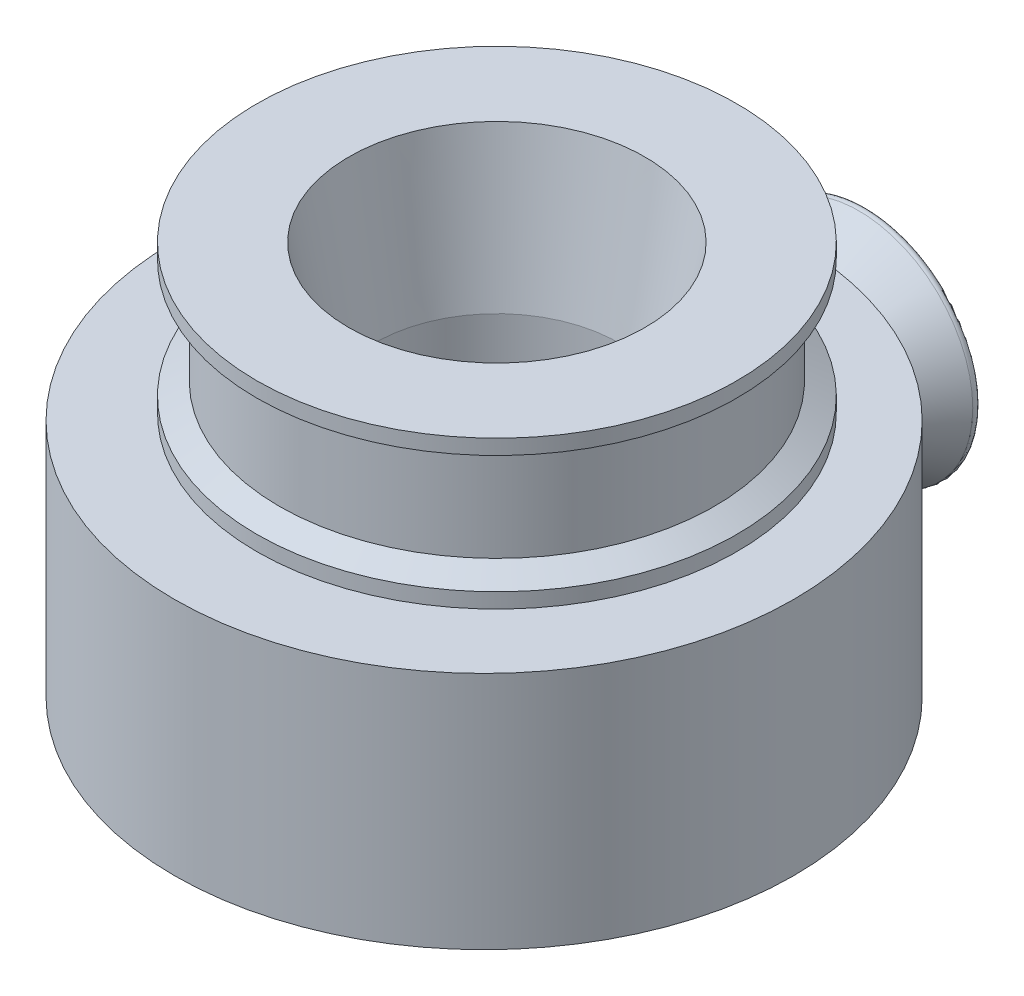
SolidWorks part; units mm, degrees
ref_plane "Front Plane" through (0, 0, 0) normal (0, 0, 1) x (1, 0, 0)
ref_plane "Top Plane" through (0, 0, 0) normal (0, 1, 0) x (1, 0, 0)
ref_plane "Right Plane" through (0, 0, 0) normal (1, 0, 0) x (0, 0, -1)
sketch "Sketch1" plane through (0, 0, 0) normal (0, 1, 0) x (1, 0, 0)
  circle A0 centre (0, 0) radius 20.65
  circle A1 centre (0, 0) radius 12.75
  dimension "D1" = 41.3
  dimension "D2" = 25.5
extrude "Boss-Extrude1" add sketch "Sketch1" along normal mid plane 15.95
sketch "Sketch2" plane through (0, 0, 0) normal (0, 1, 0) x (1, 0, 0)
  line L0 (-7.35, 25.45) -> (7.35, 25.45)
  line L1 (-4.285, 20.2005) -> (4.285, 20.2005)
  line L2 (-4.285, 20.2005) -> (-7.5966, 24.9791)
  line L3 (4.285, 20.2005) -> (7.5966, 24.9791) construction
  line L4 (0, 25.45) -> (0, 20.2005)
  line L5 (0, 0) -> (0, -7.3566) construction
  circle A0 centre (0, 0) radius 20.65 construction
  arc A1 (-7.35, 25.45) -> (-7.5966, 24.9791) centre (-7.35, 25.15) ccw
  arc A2 (7.35, 25.45) -> (7.5966, 24.9791) centre (7.35, 25.15) cw
  point P2 (0, 20.65)
  point P3 (0, 25.45)
  point P13 (7.65, 25.15)
  point P14 (-7.65, 25.15)
  dimension "D3" = 15.3
  dimension "D4" = 0.3
  dimension "D1" = 4.8
  dimension "D2" = 8.57
ref_axis "Axis1" through (0, 0, 23) along (0, 0, -1)
revolve "Revolve1" add sketch "Sketch2" angle 360 about axis through (0, 0, 23) along (0, 0, -1) region at (-3.1318, 0, -23.0808)
sketch "Sketch3" plane through (0, 0, -25.45) normal (0, 0, -1) x (-1, 0, 0)
  line L1 (0, 2.6558) -> (-2.3, 1.3279)
  line L2 (-2.3, 1.3279) -> (-2.3, -1.3279)
  line L3 (-2.3, -1.3279) -> (0, -2.6558)
  line L4 (0, -2.6558) -> (2.3, -1.3279)
  line L5 (2.3, -1.3279) -> (2.3, 1.3279)
  line L6 (2.3, 1.3279) -> (0, 2.6558)
  circle A0 centre (0, 0) radius 2.3 construction
  dimension "D1" = 4.6
extrude "Cut-Extrude1" cut sketch "Sketch3" against normal blind 4.6
sketch "Sketch4" plane through (0, 0, 0) normal (0, 1, 0) x (1, 0, 0)
  line L0 (-3.5, 12.95) -> (3.5, 12.95)
  line L1 (7.35, 25.45) -> (-7.35, 25.45) construction
  line L2 (-3.5, 12.95) -> (-4.45, 11.9482)
  line L3 (-4.45, 11.9482) -> (4.45, 11.9482)
  line L4 (4.45, 11.9482) -> (3.5, 12.95)
  line L5 (0, 12.95) -> (0, 11.9482)
  circle A0 centre (0, 0) radius 12.75 construction
  dimension "D1" = 12.5
  dimension "D2" = 8.9
  dimension "D3" = 7
revolve "Cut-Revolve2" cut sketch "Sketch4" angle 360 about axis through (0, 0, 23) along (0, 0, -1) region at (-1.997, 0, -12.4292)
sketch "Sketch5" plane through (0, 0, 0) normal (0, 1, 0) x (1, 0, 0)
  line L0 (0, -23) -> (0, 28.7) construction
  circle A0 centre (0, 0) radius 12.55
  circle A1 centre (0, 0.8509) radius 8.125
  circle A2 centre (0, 0) radius 12.75 construction
  dimension "D1" = 0.2
  dimension "D2" = 16.25
  dimension "D3" = 0.8509
extrude "Boss-Extrude2" add sketch "Sketch5" along normal up to surface and the other way up to surface separate body up to face at (0, 7.975, 20.65) other way up to face at (0, -7.975, 20.65)
sketch "Sketch9" plane through (0, 0, -25.45) normal (0, 0, -1) x (-1, 0, 0)
  circle A0 centre (0, 0) radius 3
  dimension "D1" = 6
extrude "Cut-Extrude3" cut sketch "Sketch9" against normal blind 13.97
chamfer "Chamfer1" distance 1.016 angle 45 1 edges at (-3, 0, -11.48)
mirror "Mirror2" about plane through (0, 0, 0) normal (0, 0, 1) of "Chamfer1", "Cut-Extrude3"
ref_axis "Axis2" through (0, 69.5801, -0.8509) along (0, -1, 0)
sketch "Sketch11" plane through (0, 0, 0) normal (1, 0, 0) x (0, 0, -1)
  line L0 (8.9759, 7.975) -> (10.7155, 17.841)
  line L3 (10.7155, 17.841) -> (16.8509, 17.841)
  line L4 (16.8509, 17.841) -> (16.8509, 16.841)
  line L5 (16.8509, 16.841) -> (15.3509, 16.841)
  line L6 (15.3509, 16.841) -> (15.3509, 9.841)
  line L7 (15.3509, 9.841) -> (16.8509, 8.975)
  line L8 (16.8509, 8.975) -> (16.8509, 7.975)
  line L9 (20.65, 7.975) -> (-20.65, 7.975) construction
  line L10 (16.8509, 7.975) -> (8.9759, 7.975)
  line L11 (0.8509, 69.5801) -> (0.8509, -6.875) construction
  point P13 (14.4985, 11.1845)
  point P14 (16.9161, 18.5867)
  dimension "D1" = 1
  dimension "D2" = 16
  dimension "D3" = 80
  dimension "D4" = 7
  dimension "D5" = 60
  dimension "D6" = 1.5
  dimension "D7" = 1
revolve "Revolve2" add sketch "Sketch11" angle 360 about axis through (0, 69.5801, -0.8509) along (0, -1, 0)
